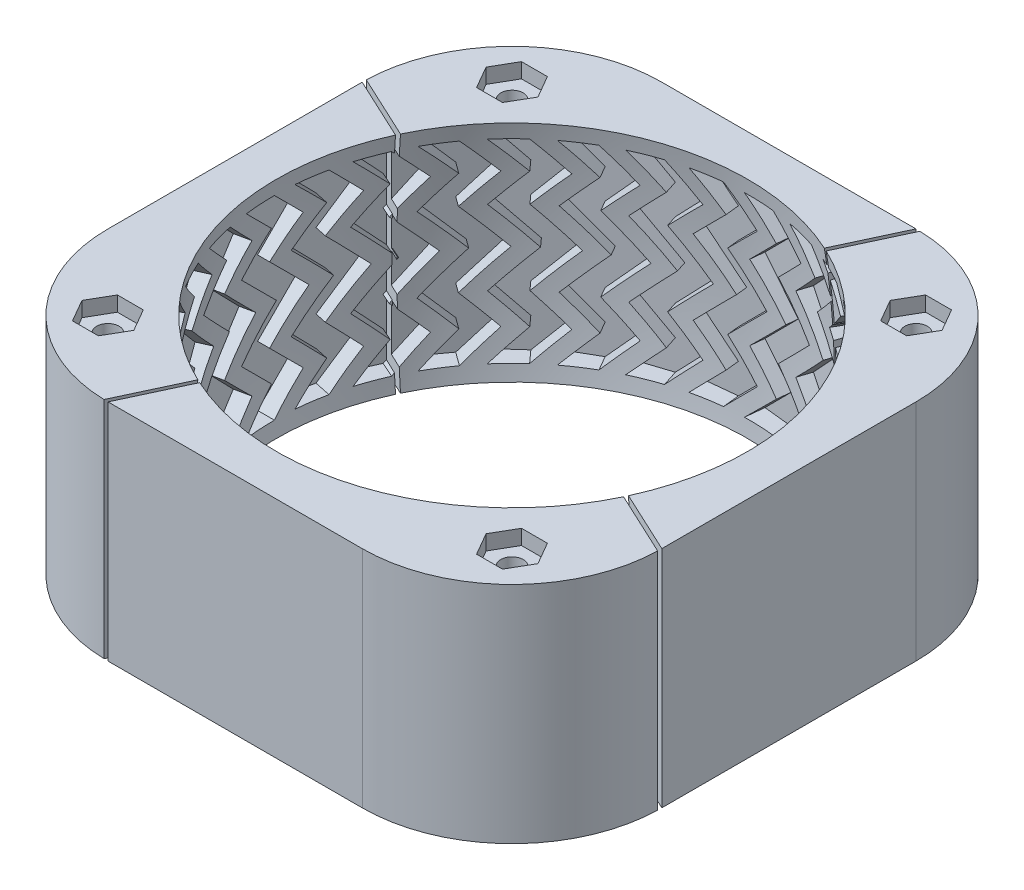
SolidWorks part; units mm, degrees
material "ABS"
ref_plane "Спереди" through (0, 0, 0) normal (0, 0, 1) x (1, 0, 0)
ref_plane "Сверху" through (0, 0, 0) normal (0, 1, 0) x (1, 0, 0)
ref_plane "Справа" through (0, 0, 0) normal (1, 0, 0) x (0, 0, -1)
sketch "Эскиз2" plane through (0, 0, 0) normal (0, 1, 0) x (1, 0, 0)
  line L1 (37, -37) -> (-37, -37)
  line L2 (37, -37) -> (37, 37)
  line L3 (37, 37) -> (-37, 37)
  line L4 (-37, -37) -> (-37, 37)
  line L5 (37, -37) -> (-37, 37) construction
  line L6 (37, 37) -> (-37, -37) construction
  point P0 (0, 0)
  dimension "D1" = 74
  dimension "D2" = 74
extrude "Бобышка-Вытянуть1" add sketch "Эскиз2" along normal blind 30
sketch "Эскиз3" plane through (0, 0, 0) normal (1, 0, 0) x (0, 0, -1)
  line L0 (0, 41.3522) -> (0, -3.1956) construction
  line L1 (-34.4708, 15) -> (34.6551, 15) construction
  line L3 (-31.5, 30) -> (-31.5, 0)
  line L5 (0, 0) -> (0, 30)
  line L7 (-37, 30) -> (37, 30) construction
  line L9 (-31.5, 30) -> (0, 30)
  line L12 (-31.5, 0) -> (0, 0)
  line L13 (-40.4768, 0) -> (40.1693, 0) construction
  line L14 (-37, 0) -> (37, 0) construction
  arc A0 (-31.5, 0) -> (-31.5, 30) centre (80.5, 15) cw
  point P7 (-32.5, 15)
  dimension "D1" = 1
  dimension "D2" = 63
revolve "Вырез-Повернуть1" cut sketch "Эскиз3" angle 360 about L0 region at (0, 15, 15.75) region at (0, 15, 31.9002)
fillet "Скругление1" radius 20 4 edges at (-37, 15, 37) (-37, 15, -37) (37, 15, -37) (37, 15, 37)
ref_plane "Плоскость5" through (31, 0, 0) normal (1, 0, 0) x (0, 0, -1)
sketch "Эскиз7" plane through (31, 0, 0) normal (1, 0, 0) x (0, 0, -1)
  line L0 (0, 44.0212) -> (0, -3.9515) construction
  line L2 (-28.1298, 15) -> (25.9038, 15) construction
  line L3 (-17, 30) -> (17, 30) construction
  line L28 (-17, 0) -> (17, 0) construction
  line L30 (-1, 15) -> (4, 20)
  line L31 (4, 20) -> (0, 24)
  line L32 (0, 24) -> (4, 28)
  line L33 (-1, 15) -> (4, 10)
  line L34 (4, 10) -> (0, 6)
  line L35 (0, 6) -> (4, 2)
  line L36 (-5, 15) -> (0, 20)
  line L37 (0, 20) -> (-4, 24)
  line L38 (-4, 24) -> (0, 28)
  line L39 (-5, 15) -> (0, 10)
  line L40 (0, 10) -> (-4, 6)
  line L41 (-4, 6) -> (0, 2)
  line L42 (0, 28) -> (4, 28)
  line L43 (0, 2) -> (4, 2)
  point P6 (0, 23.6699)
  point P12 (-1, 15)
  point P13 (-7.5623, 18)
  point P21 (0, 0)
  point P22 (-5, 15)
  dimension "D1" = 2
  dimension "D2" = 4
  dimension "D4" = 2
extrude "Вырез-Вытянуть3" cut sketch "Эскиз7" along normal blind 3 contours L33 | L43 L35 L34 L33 L30 L31 L32 L42 L38 L37 L36 L39 L40 L41
pattern_circular "Круговой массив1" count 30 over 360 about axis through (0, 30, 0) along (0, 1, 0) of "Вырез-Вытянуть3"
sketch "Эскиз17" plane through (0, 0, 0) normal (0, 1, 0) x (1, 0, 0)
  line L1 (27, -27) -> (-27, -27)
  line L2 (27, -27) -> (27, 27)
  line L3 (27, 27) -> (-27, 27)
  line L4 (-27, -27) -> (-27, 27)
  line L5 (27, -27) -> (-27, 27) construction
  line L6 (27, 27) -> (-27, -27) construction
  circle A0 centre (-27, 27) radius 1.5
  circle A1 centre (27, 27) radius 1.5
  circle A2 centre (27, -27) radius 1.5
  circle A3 centre (-27, -27) radius 1.5
  point P0 (0, 0)
  dimension "D3" = 3
  dimension "D1" = 54
  dimension "D2" = 54
extrude "Вырез-Вытянуть12" cut sketch "Эскиз17" along normal through all contours A3 | A2 | A1 | A0
sketch "Эскиз18" plane through (0, 30, 0) normal (0, 1, 0) x (1, 0, 0)
  line L1 (-28.7321, 30) -> (-30.4641, 27)
  line L2 (-30.4641, 27) -> (-28.7321, 24)
  line L3 (-28.7321, 24) -> (-25.2679, 24)
  line L4 (-25.2679, 24) -> (-23.5359, 27)
  line L5 (-23.5359, 27) -> (-25.2679, 30)
  line L6 (-25.2679, 30) -> (-28.7321, 30)
  line L7 (25.2679, 30) -> (23.5359, 27)
  line L8 (23.5359, 27) -> (25.2679, 24)
  line L9 (25.2679, 24) -> (28.7321, 24)
  line L10 (28.7321, 24) -> (30.4641, 27)
  line L11 (30.4641, 27) -> (28.7321, 30)
  line L12 (28.7321, 30) -> (25.2679, 30)
  line L13 (25.2679, -24) -> (23.5359, -27)
  line L14 (23.5359, -27) -> (25.2679, -30)
  line L15 (25.2679, -30) -> (28.7321, -30)
  line L16 (28.7321, -30) -> (30.4641, -27)
  line L17 (30.4641, -27) -> (28.7321, -24)
  line L18 (28.7321, -24) -> (25.2679, -24)
  line L19 (-28.7321, -24) -> (-30.4641, -27)
  line L20 (-30.4641, -27) -> (-28.7321, -30)
  line L21 (-28.7321, -30) -> (-25.2679, -30)
  line L22 (-25.2679, -30) -> (-23.5359, -27)
  line L23 (-23.5359, -27) -> (-25.2679, -24)
  line L24 (-25.2679, -24) -> (-28.7321, -24)
  circle A0 centre (-27, 27) radius 3 construction
  circle A1 centre (27, 27) radius 3 construction
  circle A2 centre (27, -27) radius 3 construction
  circle A3 centre (-27, -27) radius 3 construction
  dimension "D1" = 6
extrude "Вырез-Вытянуть13" cut sketch "Эскиз18" against normal blind 2
sketch "Эскиз19" plane through (0, 0, 0) normal (0, 1, 0) x (1, 0, 0)
  line L1 (-28.7321, -30) -> (-25.2679, -30)
  line L2 (-25.2679, -30) -> (-23.5359, -27)
  line L3 (-23.5359, -27) -> (-25.2679, -24)
  line L4 (-25.2679, -24) -> (-28.7321, -24)
  line L5 (-28.7321, -24) -> (-30.4641, -27)
  line L6 (-30.4641, -27) -> (-28.7321, -30)
  line L7 (25.2679, -30) -> (28.7321, -30)
  line L8 (28.7321, -30) -> (30.4641, -27)
  line L9 (30.4641, -27) -> (28.7321, -24)
  line L10 (28.7321, -24) -> (25.2679, -24)
  line L11 (25.2679, -24) -> (23.5359, -27)
  line L12 (23.5359, -27) -> (25.2679, -30)
  line L13 (25.2679, 24) -> (28.7321, 24)
  line L14 (28.7321, 24) -> (30.4641, 27)
  line L15 (30.4641, 27) -> (28.7321, 30)
  line L16 (28.7321, 30) -> (25.2679, 30)
  line L17 (25.2679, 30) -> (23.5359, 27)
  line L18 (23.5359, 27) -> (25.2679, 24)
  line L19 (-28.7321, 24) -> (-25.2679, 24)
  line L20 (-25.2679, 24) -> (-23.5359, 27)
  line L21 (-23.5359, 27) -> (-25.2679, 30)
  line L22 (-25.2679, 30) -> (-28.7321, 30)
  line L23 (-28.7321, 30) -> (-30.4641, 27)
  line L24 (-30.4641, 27) -> (-28.7321, 24)
  circle A0 centre (-27, -27) radius 3 construction
  circle A1 centre (27, -27) radius 3 construction
  circle A2 centre (27, 27) radius 3 construction
  circle A3 centre (-27, 27) radius 3 construction
  dimension "D1" = 6
extrude "Вырез-Вытянуть15" cut sketch "Эскиз19" along normal blind 2
sketch "Эскиз20" plane through (0, 0, 0) normal (0, 1, 0) x (1, 0, 0)
  line L0 (17.2994, 37.0987) -> (-17.2994, -37.0987) construction
  line L2 (0, 52.456) -> (0, -68.5486) construction
  line L3 (-17.0728, -37.2044) -> (-17.526, -36.9931)
  line L4 (-17.0728, -37.2044) -> (17.526, 36.9931)
  line L5 (17.526, 36.9931) -> (17.0728, 37.2044)
  line L6 (-17.526, -36.9931) -> (17.0728, 37.2044)
  line L7 (-17.0728, -37.2044) -> (17.0728, 37.2044) construction
  line L8 (17.526, 36.9931) -> (-17.526, -36.9931) construction
  line L9 (-37.2044, 17.0728) -> (36.9931, -17.526)
  line L10 (-37.2044, 17.0728) -> (-36.9931, 17.526)
  line L11 (-36.9931, 17.526) -> (37.2044, -17.0728)
  line L12 (36.9931, -17.526) -> (37.2044, -17.0728)
  line L13 (17.0728, 37.2044) -> (-17.526, -36.9931)
  line L14 (17.0728, 37.2044) -> (17.526, 36.9931)
  line L15 (17.526, 36.9931) -> (-17.0728, -37.2044)
  line L16 (-17.526, -36.9931) -> (-17.0728, -37.2044)
  line L17 (37.2044, -17.0728) -> (-36.9931, 17.526)
  line L18 (37.2044, -17.0728) -> (36.9931, -17.526)
  line L19 (36.9931, -17.526) -> (-37.2044, 17.0728)
  line L20 (-36.9931, 17.526) -> (-37.2044, 17.0728)
  arc A0 (-37, -17) -> (-17, -37) centre (-17, -17) ccw construction
  arc A1 (37, 17) -> (17, 37) centre (17, 17) ccw construction
  point P20 (17.2994, 37.0987)
  point P30 (0, 0)
  dimension "D1" = 0.5
  dimension "D2" = 4
  dimension "D3" = 25
extrude "Вырез-Вытянуть16" cut sketch "Эскиз20" along normal through all contours L4 L6 L3 | L4 L5 L6 | L6 | L4 region at (-8.7025, 0, 18.6627) region at (18.6627, 0, 8.7025) region at (-18.6627, 0, -8.7025) region at (8.7025, 0, -18.6627)
sketch "Эскиз21" plane through (0, 0, 0) normal (0, 1, 0) x (1, 0, 0)
  line L0 (-33.3728, 46.9354) -> (33.9176, 46.9354)
  line L1 (46.9354, 33.3728) -> (46.9354, -33.9176)
  line L2 (33.3728, -46.9354) -> (-33.9176, -46.9354)
  line L3 (-46.9354, -33.3728) -> (-46.9354, 33.9176)
  arc A0 (-17, 37) -> (-36.9931, 17.526) centre (-17, 17) ccw construction
  arc A1 (37, 17) -> (17.526, 36.9931) centre (17, 17) ccw construction
  arc A2 (17, -37) -> (36.9931, -17.526) centre (17, -17) ccw construction
  arc A3 (-37, -17) -> (-17.526, -36.9931) centre (-17, -17) ccw construction
  arc A4 (-17, 37) -> (-36.9931, 17.526) centre (-17, 17) ccw
  arc A5 (37, 17) -> (17.526, 36.9931) centre (17, 17) ccw
  arc A6 (17, -37) -> (36.9931, -17.526) centre (17, -17) ccw
  arc A7 (-37, -17) -> (-17.526, -36.9931) centre (-17, -17) ccw
  circle A8 centre (0.2724, 83.9219) radius 50
  circle A9 centre (83.9219, -0.2724) radius 50
  circle A10 centre (-0.2724, -83.9219) radius 50
  circle A11 centre (-83.9219, 0.2724) radius 50
  point P31 (0, 0)
  dimension "D1" = 100
  dimension "D2" = 4
extrude "Вырез-Вытянуть17" [suppressed] cut sketch "Эскиз21" along normal through all contours A8 L0 | L3 A11 | L1 A9 | L2 A10
equation "\"D2@Эскиз2\"=\"D1@Эскиз2\""
equation "\"D2@Эскиз17\"=\"D1@Эскиз17\""
